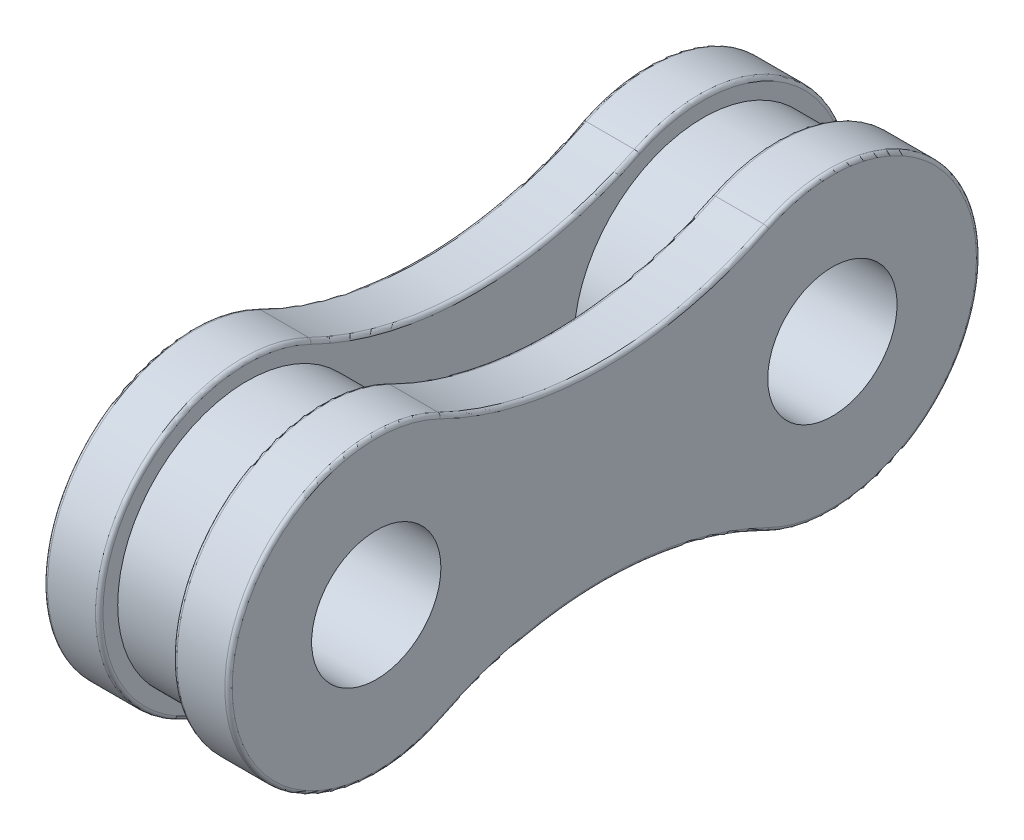
SolidWorks part; units mm, degrees
ref_plane "Front Plane" through (0, 0, 0) normal (0, 0, 1) x (1, 0, 0)
ref_plane "Top Plane" through (0, 0, 0) normal (0, 1, 0) x (1, 0, 0)
ref_plane "Right Plane" through (0, 0, 0) normal (1, 0, 0) x (0, 0, -1)
sketch "Sketch1" plane through (0, 0, 0) normal (1, 0, 0) x (0, 0, -1)
  line L0 (6175, 0) -> (-6175, 0) construction
  line L1 (0, -12265.2787) -> (0, 12284.0066) construction
  arc A0 (-4410.7143, 3589.888) -> (-4410.7143, -3589.888) centre (-6175, 0) ccw
  circle A1 centre (-6175, 0) radius 1750
  circle A2 centre (6175, 0) radius 1750
  arc A3 (4410.7143, 3589.888) -> (4410.7143, -3589.888) centre (6175, 0) cw
  arc A4 (-4410.7143, 3589.888) -> (4410.7143, 3589.888) centre (0, 12564.608) ccw
  arc A5 (-4410.7143, -3589.888) -> (4410.7143, -3589.888) centre (0, -12564.608) cw
  point P5 (-3955.6954, 3363.0836)
  point P8 (0, 0)
  dimension "D2" = 8000
  dimension "D3" = 3500
  dimension "D4" = 10000
  dimension "D1" = 12350
extrude "Boss-Extrude1" add sketch "Sketch1" along normal blind 1500 from offset 1000
sketch "Sketch2" plane through (0, 0, 0) normal (1, 0, 0) x (0, 0, -1)
  circle A0 centre (-6175, 0) radius 1750 construction
  circle A1 centre (6175, 0) radius 1750 construction
  circle A2 centre (-6175, 0) radius 1750
  circle A3 centre (6175, 0) radius 1750
  arc A4 (4410.7143, -3589.888) -> (-4410.7143, -3589.888) centre (0, -12564.608) ccw
  arc A5 (4410.7143, -3589.888) -> (4410.7143, 3589.888) centre (6175, 0) ccw
  arc A6 (-4410.7143, 3589.888) -> (4410.7143, 3589.888) centre (0, 12564.608) ccw
  arc A7 (-4410.7143, 3589.888) -> (-4410.7143, -3589.888) centre (-6175, 0) ccw
  arc A8 (4410.7143, -3589.888) -> (-4410.7143, -3589.888) centre (0, -12564.608) ccw
  arc A9 (4410.7143, -3589.888) -> (4410.7143, 3589.888) centre (6175, 0) ccw
  arc A10 (-4410.7143, 3589.888) -> (4410.7143, 3589.888) centre (0, 12564.608) ccw
  arc A11 (-4410.7143, 3589.888) -> (-4410.7143, -3589.888) centre (-6175, 0) ccw
  dimension "D1" = 0
extrude "Boss-Extrude2" add sketch "Sketch2" against normal blind 1500 from offset 1000 separate body offset against normal yes
sketch "Sketch3" plane through (0, 0, 0) normal (1, 0, 0) x (0, 0, -1)
  line L0 (0, -1146.9345) -> (0, 5479.7981) construction
  circle A0 centre (6175, 0) radius 1750 construction
  circle A1 centre (-6175, 0) radius 1750 construction
  circle A2 centre (6175, 0) radius 1750
  circle A3 centre (-6175, 0) radius 1750
  circle A4 centre (6175, 0) radius 3500
  circle A5 centre (-6175, 0) radius 3500
  dimension "D1" = 7000
extrude "Boss-Extrude3" add sketch "Sketch3" along normal mid plane 2000
fillet "Fillet1" radius 100 16 edges at (2500, 0, 10175) (2500, 2564.608, 0) (2500, 0, -10175) (1000, 0, 10175) (1000, 2564.608, 0) (1000, 0, -10175) (-1000, 0, 10175) (-1000, 2564.608, 0) (-1000, 0, -10175) (-2500, 0, 10175) (-2500, 2564.608, 0) (-2500, 0, -10175) (2500, -2564.608, 0) (1000, -2564.608, 0) (-1000, -2564.608, 0) (-2500, -2564.608, 0)
